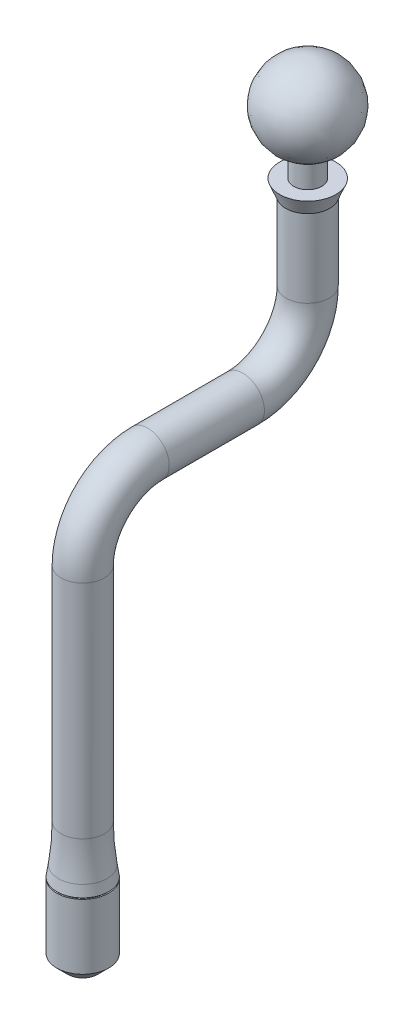
SolidWorks part; units mm, degrees
ref_plane "Front Plane" through (0, 0, 0) normal (0, 0, 1) x (1, 0, 0)
ref_plane "Top Plane" through (0, 0, 0) normal (0, 1, 0) x (1, 0, 0)
ref_plane "Right Plane" through (0, 0, 0) normal (1, 0, 0) x (0, 0, -1)
sketch "Sketch2" plane through (0, 0, 0) normal (1, 0, 0) x (0, 0, -1)
  line L0 (0, 0) -> (0, 18)
  line L1 (-37, -15) -> (-15, -15)
  line L2 (-52, -30) -> (-52, -85)
  arc A0 (0, 0) -> (-15, -15) centre (-15, 0) cw
  arc A1 (-37, -15) -> (-52, -30) centre (-37, -30) ccw
  dimension "D2" = 15
  dimension "D1" = 18
  dimension "D3" = 52
  dimension "D4" = 55
sweep "Sweep1" add path "Sketch2" circular profile diameter 10 parameters "D3"=10
sketch "Sketch11" plane through (0, -85, 0) normal (0, -1, 0) x (1, 0, 0)
  circle A0 centre (0, 52) radius 5
ref_plane "Plane1" through (0, -92.3, 0) normal (0, -1, 0) x (-1, 0, 0)
sketch "Sketch12" plane through (0, -92.3, 0) normal (0, -1, 0) x (-1, 0, 0)
  circle A0 centre (0, -52) radius 6
  dimension "D1" = 12
loft "Loft1" add profiles "Sketch11", "Sketch12" connector at (0, -85, 47) connector at (1.5205, -92.3, 46.1959)
fillet "Fillet1" radius 60 1 edges at (0, -85, 47)
sketch "Sketch13" plane through (0, -92.3, 0) normal (0, -1, 0) x (1, 0, 0)
  circle A0 centre (0, 52) radius 5.7
  dimension "D1" = 11.4
extrude "Boss-Extrude1" add sketch "Sketch13" along normal blind 0.3
sketch "Sketch14" plane through (0, -92.6, 0) normal (0, -1, 0) x (1, 0, 0)
  circle A0 centre (0, 52) radius 6
  circle A1 centre (0, 52) radius 5.7 construction
  dimension "D1" = 12
extrude "Boss-Extrude2" add sketch "Sketch14" along normal blind 15
ref_plane "Plane2" through (0, -110.1, 0) normal (0, -1, 0) x (-1, 0, 0)
sketch "Sketch15" plane through (0, -110.1, 0) normal (0, -1, 0) x (-1, 0, 0)
  circle A0 centre (0, -52) radius 3.5
  circle A1 centre (0, -52) radius 6 construction
  dimension "D1" = 7
sketch "Sketch16" plane through (0, -107.6, 0) normal (0, -1, 0) x (1, 0, 0)
  circle A0 centre (0, 52) radius 6
  circle A1 centre (0, 52) radius 6 construction
  dimension "D1" = 12
loft "Loft2" add profiles "Sketch15", "Sketch16" connector at (0, -110.1, 48.5) connector at (0, -107.6, 46)
sketch "Sketch17" plane through (0, -110.1, 0) normal (0, -1, 0) x (1, 0, 0)
  circle A0 centre (0, 52) radius 0.75
  circle A1 centre (0, 52) radius 3.5 construction
  dimension "D1" = 1.5
extrude "Cut-Extrude1" cut sketch "Sketch17" against normal blind 30
sketch "Sketch18" plane through (0, 0, 0) normal (1, 0, 0) x (0, 0, -1)
  line L2 (6.5, 21.5) -> (5.0783, 18)
  line L3 (0, 18) -> (5.0783, 18)
  line L4 (0, 18) -> (0, 21.5)
  line L5 (5, 18) -> (-5, 18) construction
  line L6 (3.25, 21.5) -> (6.5, 21.5)
  line L7 (3.25, 21.5) -> (3.25, 27.059)
  line L8 (0, 21.5) -> (0, 45.5884)
  arc A0 (3.25, 27.059) -> (0, 45.5884) centre (0.4, 36.1088) ccw
  dimension "D1" = 6.5
  dimension "D2" = 3.5
sketch "Sketch19" plane through (0, 0, 0) normal (1, 0, 0) x (0, 0, -1)
  line L0 (0, 0) -> (0, 29.6018) construction
revolve "Revolve1" add sketch "Sketch18" angle 360 about L0
